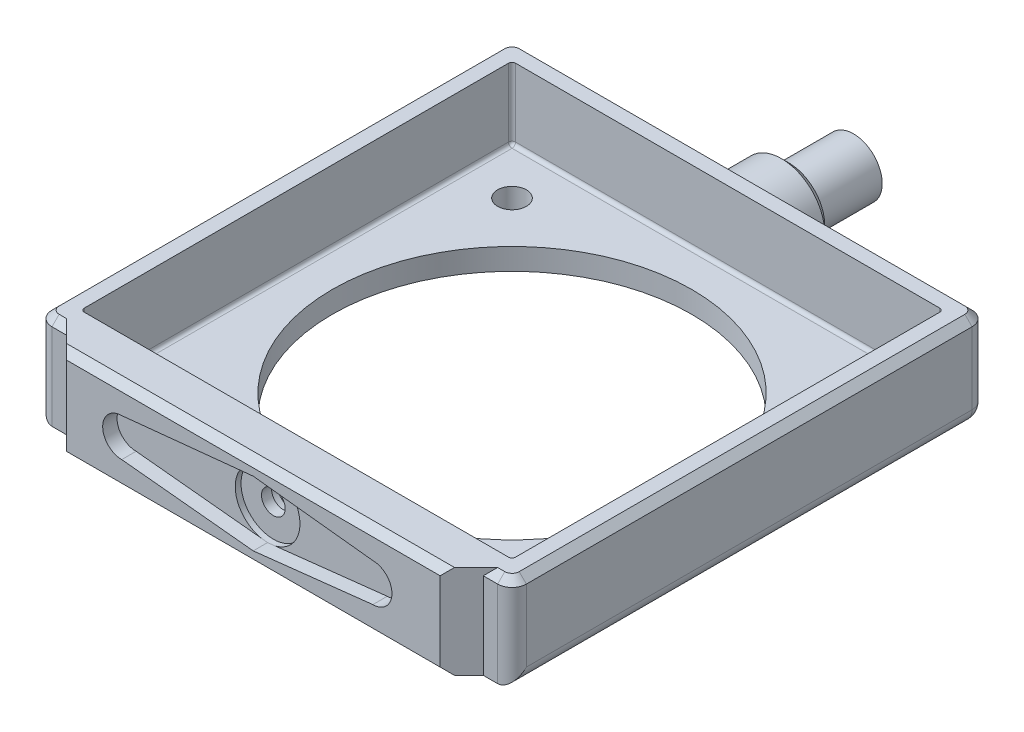
SolidWorks part; units mm, degrees
ref_plane "Front Plane" through (0, 0, 0) normal (0, 0, 1) x (1, 0, 0)
ref_plane "Top Plane" through (0, 0, 0) normal (0, 1, 0) x (1, 0, 0)
ref_plane "Right Plane" through (0, 0, 0) normal (1, 0, 0) x (0, 0, -1)
sketch "Sketch1" plane through (0, 0, 0) normal (0, 1, 0) x (1, 0, 0)
  line L1 (-30, -30) -> (30, -30)
  line L2 (-30, -30) -> (-30, 30)
  line L3 (-30, 30) -> (30, 30)
  line L4 (30, -30) -> (30, 30)
  line L5 (-33, -33) -> (33, -33)
  line L6 (-33, -33) -> (-33, 33)
  line L7 (-33, 33) -> (33, 33)
  line L8 (33, -33) -> (33, 33)
extrude "Boss-Extrude1" add sketch "Sketch1" along normal blind 13
sketch "Sketch2" plane through (0, 0, 0) normal (0, 1, 0) x (1, 0, 0)
  line L1 (-30, -30) -> (30, -30)
  line L2 (-30, -30) -> (-30, 30)
  line L3 (-30, 30) -> (30, 30)
  line L4 (30, -30) -> (30, 30)
  circle A0 centre (0, 0) radius 25
  circle A1 centre (-23.5, 23.5) radius 2
  circle A2 centre (23.5, 23.5) radius 2
  circle A3 centre (23.5, -23.5) radius 2
  circle A4 centre (-23.5, -23.5) radius 2
  point P20 (0, 0)
  dimension "D1" = 4
extrude "Boss-Extrude2" add sketch "Sketch2" along normal blind 3
sketch "Sketch8" plane through (0, 0, 0) normal (0, 0, 1) x (1, 0, 0)
  circle A0 centre (0, 6.5) radius 14
fillet "Fillet1" radius 0.5 8 edges at (30, 8, 30) (30, 3, 0) (30, 8, -30) (0, 3, -30) (-30, 8, -30) (-30, 8, 30) (-30, 3, 0) (0, 3, 30)
fillet "Fillet2" radius 2 7 edges at (-33, 6.5, -33) (-33, 0, 0) (-33, 6.5, 33) (33, 6.5, 33) (33, 0, 0) (0, 0, -33) (33, 6.5, -33)
sketch "Sketch10" plane through (0, 0, 33) normal (0, 0, 1) x (1, 0, 0)
  circle A0 centre (0, 6.5) radius 1.65
  dimension "D1" = 3.3
sketch "Sketch12" plane through (0, 0, 33) normal (0, 0, 1) x (1, 0, 0)
  line L0 (-31, 13) -> (-31, 0) construction
  line L1 (-26, 12) -> (26, 12)
  line L2 (-26, 12) -> (-26, 1)
  line L3 (-26, 1) -> (26, 1)
  line L4 (26, 12) -> (26, 1)
  line L5 (-26, 12) -> (26, 1) construction
  line L6 (-26, 1) -> (26, 12) construction
  line L7 (-31, 13) -> (31, 13) construction
  point P0 (0, 6.5)
  dimension "D1" = 5
  dimension "D2" = 1
extrude "Boss-Extrude3" add sketch "Sketch12" along normal blind 3
chamfer "Chamfer1" distance 3 angle 45 4 edges at (0, 1, 33) (26, 6.5, 33) (0, 12, 33) (-26, 6.5, 33)
extrude "Cut-Extrude4" cut sketch "Sketch10" against normal blind 12 and the other way blind 12
sketch "Sketch13" plane through (0, 0, 30) normal (0, 0, -1) x (-1, 0, 0)
  circle A0 centre (0, 6.5) radius 3.05
  dimension "D1" = 6.1
extrude "Cut-Extrude6" cut sketch "Sketch13" against normal blind 1.8
sketch "Sketch14" plane through (0, 0, -33) normal (0, 0, -1) x (-1, 0, 0)
  circle A0 centre (0, 6.5) radius 4
  dimension "D1" = 8
extrude "Boss-Extrude4" add sketch "Sketch14" along normal blind 14.5
sketch "Sketch15" plane through (0, 0, -33) normal (0, 0, -1) x (-1, 0, 0)
  circle A0 centre (0, 6.5) radius 6
  circle A1 centre (0, 6.5) radius 4 construction
  dimension "D1" = 2
extrude "Boss-Extrude5" add sketch "Sketch15" along normal blind 5.5 and the other way blind 2
chamfer "Chamfer2" distance 1 angle 45 1 edges at (-6, 6.5, -38.5)
chamfer "Chamfer3" distance 1 angle 45 9 edges at (30, 13, 33) (-30, 13, 33) (32.4142, 13, 32.4142) (-32.4142, 13, 32.4142) (33, 13, 0) (-33, 13, 0) (32.4142, 13, -32.4142) (-32.4142, 13, -32.4142) (0, 13, -33)
sketch "Sketch17" plane through (0, 0, 36) normal (0, 0, 1) x (1, 0, 0)
  line L0 (-18.2936, 9.15) -> (0, 11)
  line L1 (0, 11) -> (16.644, 9.15)
  line L2 (-18.2936, 3.85) -> (0, 2)
  line L3 (0, 2) -> (16.644, 3.85)
  circle A0 centre (0, 6.5) radius 4.5
  circle A1 centre (16.644, 6.5) radius 2.65
  circle A2 centre (-18.2936, 6.5) radius 2.65
  circle M1 centre (0, 6.5) radius 1.65
  dimension "D1" = 9
  dimension "D2" = 5.3
  dimension "D3" = 5.3
extrude "Cut-Extrude8" cut sketch "Sketch17" against normal blind 2 contours A2 | A2 L2 A0 L0 | L0 A0 L2 L3 L1 M1 | A1 L1 A0 L3 | A1 region at (-9.5819, 6.5, 36) region at (-18.2936, 6.5, 36) region at (-0.4377, 10.8278, 36) region at (8.832, 6.5, 36) region at (16.644, 6.5, 36)
sketch "Sketch18" plane through (0, 0, 34) normal (0, 0, 1) x (1, 0, 0)
  circle A0 centre (0, 6.5) radius 4.5
extrude "Cut-Extrude9" cut sketch "Sketch18" against normal blind 0.8
